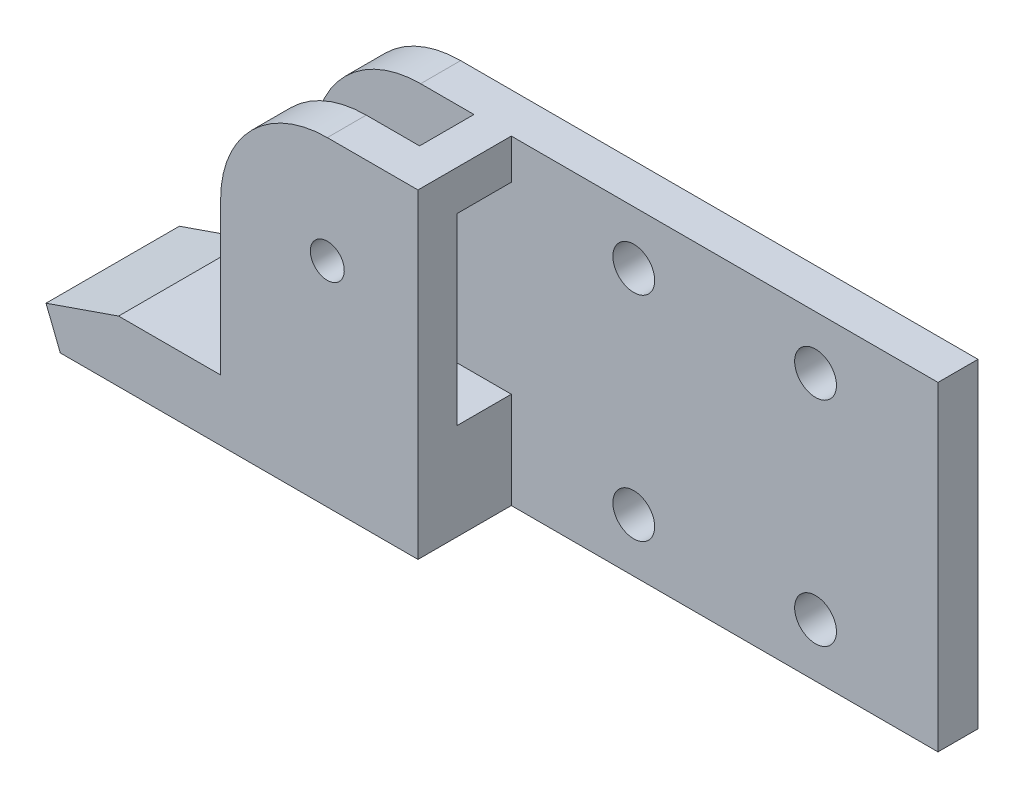
SolidWorks part; units mm, degrees
note: The reader was unsure of these and kept them because the rebuilt part matched: shared geometry of "Sketch12<3>".
ref_plane "Front Plane" through (0, 0, 0) normal (0, 0, 1) x (1, 0, 0)
ref_plane "Top Plane" through (0, 0, 0) normal (0, 1, 0) x (1, 0, 0)
ref_plane "Right Plane" through (0, 0, 0) normal (1, 0, 0) x (0, 0, -1)
sketch "Sketch2" plane through (0, 0, 0) normal (0, 0, 1) x (1, 0, 0)
  line L0 (-36.2055, -212.6584) -> (-69.6869, -224.2524) construction
  line L4 (25.4, -305.6274) -> (25.4, 320.675) construction
  line L7 (-67.9862, -228.5334) -> (-69.6869, -224.2524)
  line L8 (-48.895, -221.2606) -> (-48.895, -203.1334)
  line L10 (-36.195, -190.4334) -> (25.4, -190.4334)
  line L13 (-69.6869, -224.2524) -> (-61.047, -221.2606)
  line L15 (25.4, -190.4334) -> (25.4, -228.5334)
  line L16 (25.4, -228.5334) -> (-67.9862, -228.5334)
  line L17 (-61.047, -221.2606) -> (-48.895, -221.2606)
  line L18 (-25.4, -190.4334) -> (-25.4, -228.5334) construction
  circle A0 centre (-36.195, -203.1334) radius 3.175
  circle A1 centre (-36.195, -203.1334) radius 39.5944 construction
  arc A2 (-74.6371, -212.6159) -> (-69.6869, -224.2524) centre (-36.195, -203.1334) ccw construction
  arc A4 (-36.195, -190.4334) -> (-48.895, -203.1334) centre (-36.195, -203.1334) ccw
  point P16 (-48.895, -217.0525)
  dimension "D1" = 12.7
  dimension "D2" = 79.1888
  dimension "D3" = 50.8
  dimension "D4" = 4.208
extrude "Boss-Extrude1" add sketch "Sketch2" along normal blind 4.7625
sketch "Sketch4" plane through (61.8785, -178.6935, 0) normal (-0.3272, 0.9449, 0) x (0.9449, 0.3272, 0)
  line L1 (-95.8313, 4.7625) -> (-140.1004, 4.7625) construction
  line L2 (-136.6903, 4.7625) -> (-136.6903, 2.3812) construction
  line L3 (-136.6903, 4.7625) -> (-139.2303, 4.7625) construction
  line L4 (-139.2303, -4.7625) -> (-139.2303, 0) construction
  dimension "D1" = 2.54
hole_wizard "3/16 (0.1875) Diameter Hole1" [suppressed] positions "Sketch9" profile "Sketch10" hole size "3/16" standard "ANSI Inch"
sketch "Sketch9" plane through (61.8785, -178.6935, 0) normal (-0.3272, 0.9449, 0) x (0.9449, 0.3272, 0)
  point P0 (-136.6903, 2.3812)
sketch "Sketch10" plane through (-67.2867, -223.4212, -2.3812) normal (0, 0, 1) x (-0.9449, -0.3272, 0)
  line L0 (0, 0) -> (0, 3.9708)
  line L1 (0, 3.9708) -> (2.3812, 2.54)
  line L2 (2.3812, 2.54) -> (2.3812, 0)
  line L5 (2.3812, 0) -> (0, 0)
  line L10 (0, 3.9708) -> (-2.3812, 2.54) construction
  line L11 (0, -6.35) -> (0, 107.95) construction
  dimension "Hole Dia." = 4.7625
  dimension "Hole Depth" = 2.54
  dimension "Drill Angle" = 118
sketch "Sketch11" plane through (0, 0, 4.7625) normal (0, 0, -1) x (-1, 0, 0)
  line L0 (-25.4, -190.4334) -> (25.4, -190.4334) construction
  line L1 (-25.4, -190.4334) -> (36.195, -190.4334) construction
  line L2 (25.4, -190.4334) -> (25.4, -228.5334)
  line L3 (67.9862, -228.5334) -> (-25.4, -228.5334) construction
  line L4 (25.4, -228.5334) -> (67.9862, -228.5334)
  line L5 (67.9862, -228.5334) -> (69.6869, -224.2524)
  line L6 (69.6869, -224.2524) -> (61.047, -221.2606)
  line L7 (61.047, -221.2606) -> (48.895, -221.2606)
  line L8 (48.895, -221.2606) -> (48.895, -203.1334)
  line L9 (36.195, -190.4334) -> (25.4, -190.4334)
  arc A0 (48.895, -203.1334) -> (36.195, -190.4334) centre (36.195, -203.1334) ccw
  arc A1 (48.895, -203.1334) -> (36.195, -190.4334) centre (36.195, -203.1334) ccw construction
extrude "Boss-Extrude2" add sketch "Sketch11" against normal blind 11.1125
sketch "Sketch12" plane through (-48.895, 0, 0) normal (-1, 0, 0) x (0, 0, 1)
  line L3 (4.7625, -217.0525) -> (4.7625, -190.4334)
  line L9 (4.7625, -221.2606) -> (4.7625, -217.0525) construction
  line L10 (4.7625, -195.1959) -> (11.2395, -195.1959)
  line L11 (11.2395, -217.0525) -> (4.7625, -217.0525)
  line L12 (11.2395, -190.4334) -> (11.2395, -217.0525)
  line L13 (4.7625, -190.4334) -> (11.2395, -190.4334)
  line M17 (15.875, -203.1334) -> (0, -203.1334)
extrude "Cut-Extrude1" cut sketch "Sketch12" against normal blind 24.13 contours L12 L3 L11 M17 | L12 L10 L3 M17
extrude "Cut-Extrude2" cut sketch "Sketch12<3>" against normal blind 19.05 contours L13 L3 L10 L12
sketch "Sketch12<3>" plane through (-48.895, 0, 0) normal (-1, 0, 0) x (0, 0, 1) same geometry as "Sketch12"
hole_wizard "Tap Drill for #10-32 Tap1" positions "Sketch13" profile "Sketch14" hole size "#10-32" standard "ANSI Inch" end condition through all
sketch "Sketch13" plane through (0, 0, 11.2395) normal (0, 0, 1) x (1, 0, 0)
  point P0 (-36.195, -203.1334)
sketch "Sketch14" plane through (-36.195, -203.1334, 11.2395) normal (1, 0, 0) x (0, 1, 0)
  line L0 (0, 0) -> (0, 4.6355)
  line L1 (0, 4.6355) -> (2.0193, 4.6355)
  line L2 (2.0193, 4.6355) -> (2.0193, 0)
  line L5 (2.0193, 0) -> (0, 0)
  line L11 (0, -6.35) -> (0, 107.95) construction
  dimension "Thru Hole Dia." = 4.0386
  dimension "Thru Hole Depth" = 4.6355
sketch "Sketch15" plane through (0, 0, 4.7625) normal (0, 0, 1) x (1, 0, 0)
  line L0 (-25.4, -190.4334) -> (25.4, -228.5334) construction
  line L1 (0, -209.4834) -> (10.8204, -209.4834) construction
  line L2 (0, -209.4834) -> (0, -204.4261) construction
  line L3 (0, -209.4834) -> (-10.8204, -209.4834) construction
  line L4 (10.8204, -209.4834) -> (10.8204, -196.7834) construction
  line L5 (10.8204, -209.4834) -> (10.8204, -222.1834) construction
  line L6 (-10.8204, -209.4834) -> (-10.8204, -196.7834) construction
  line L7 (-10.8204, -209.4834) -> (-10.8204, -222.1834) construction
  dimension "D1" = 21.6408
  dimension "D2" = 25.4
  dimension "D3" = 25.4
hole_wizard "#10 Clearance Hole2" positions "Sketch16" profile "Sketch17" hole size "#10" standard "ANSI Inch" end condition through all
sketch "Sketch16" plane through (0, 0, 4.7625) normal (0, 0, 1) x (1, 0, 0)
  point P0 (-10.8204, -196.7834)
  point P3 (-10.8204, -222.1834)
  point P6 (10.8204, -222.1834)
  point P9 (10.8204, -196.7834)
sketch "Sketch17" plane through (-10.8204, -196.7834, 4.7625) normal (1, 0, 0) x (0, -1, 0)
  line L0 (0, 0) -> (0, 4.7625)
  line L1 (0, 4.7625) -> (2.4892, 4.7625)
  line L2 (2.4892, 4.7625) -> (2.4892, 0)
  line L5 (2.4892, 0) -> (0, 0)
  line L11 (0, -6.35) -> (0, 107.95) construction
  dimension "Thru Hole Dia." = 4.9784
  dimension "Thru Hole Depth" = 4.7625
